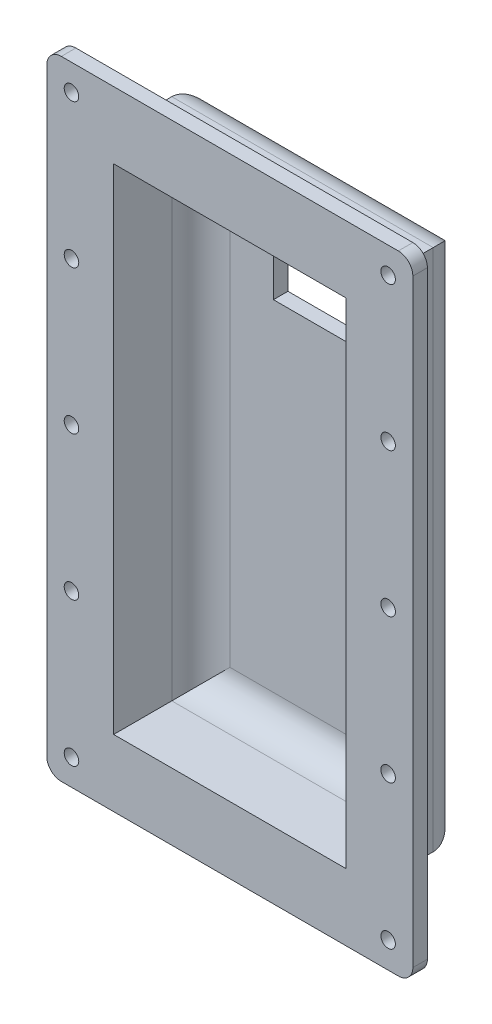
SolidWorks part; units mm, degrees
ref_plane "Front Plane" through (0, 0, 0) normal (0, 0, 1) x (1, 0, 0)
ref_plane "Top Plane" through (0, 0, 0) normal (0, 1, 0) x (1, 0, 0)
ref_plane "Right Plane" through (0, 0, 0) normal (1, 0, 0) x (0, 0, -1)
sketch "Sketch1" plane through (0, 0, 0) normal (0, 0, 1) x (1, 0, 0)
  line L1 (-22.48, 45) -> (22.48, 45)
  line L2 (-22.48, 45) -> (-22.48, -45)
  line L3 (-22.48, -45) -> (22.48, -45)
  line L4 (22.48, 45) -> (22.48, -45)
  line L5 (-22.48, 45) -> (22.48, -45) construction
  line L6 (-22.48, -45) -> (22.48, 45) construction
  point P0 (0, 0)
  dimension "D1" = 44.96
  dimension "D2" = 90
extrude "Boss-Extrude1" add sketch "Sketch1" along normal blind 15
sketch "Sketch2" plane through (0, 0, 15) normal (0, 0, 1) x (1, 0, 0)
  line L0 (-22.48, 45) -> (22.48, 45) construction
  line L1 (-31.48, 54) -> (31.48, 54)
  line L2 (-31.48, 54) -> (-31.48, -54)
  line L3 (-31.48, -54) -> (31.48, -54)
  line L4 (31.48, 54) -> (31.48, -54)
  line L5 (-31.48, 54) -> (31.48, -54) construction
  line L6 (-31.48, -54) -> (31.48, 54) construction
  line L7 (-22.48, 45) -> (-22.48, -45) construction
  point P0 (0, 0)
  point P8 (0, 45)
  dimension "D1" = 9
  dimension "D2" = 9
extrude "Boss-Extrude2" add sketch "Sketch2" along normal blind 2.5
shell "Shell1" thickness 2.5 removed face at (0, 0, 17.5)
fillet "Fillet1" radius 2.5 4 edges at (-31.48, -54, 16.25) (31.48, -54, 16.25) (31.48, 54, 16.25) (-31.48, 54, 16.25)
fillet "Fillet2" radius 5 8 edges at (0, -42.5, 2.5) (19.98, 0, 2.5) (-19.98, 0, 2.5) (0, 42.5, 2.5) (0, -45, 0) (22.48, 0, 0) (0, 45, 0) (-22.48, 0, 0)
sketch "Sketch3" plane through (0, 0, 2.5) normal (0, 0, 1) x (1, 0, 0)
  line L1 (-7.5, 29) -> (7.5, 29)
  line L2 (-7.5, 29) -> (-7.5, 21)
  line L3 (-7.5, 21) -> (7.5, 21)
  line L4 (7.5, 29) -> (7.5, 21)
  line L5 (-7.5, 29) -> (7.5, 21) construction
  line L6 (-7.5, 21) -> (7.5, 29) construction
  point P0 (0, 25)
  dimension "D1" = 8
  dimension "D2" = 15
  dimension "D3" = 25
extrude "Cut-Extrude1" cut sketch "Sketch3" against normal through all
sketch "Sketch4" plane through (0, 0, 17.5) normal (0, 0, 1) x (1, 0, 0)
  line L0 (22.48, 45) -> (22.48, -45) construction
  line L3 (-27.23, -49.5) -> (27.23, -49.5) construction
  line L10 (-27.23, -49.5) -> (-27.23, 49.5) construction
  line L11 (-27.23, 49.5) -> (27.23, 49.5) construction
  line L12 (27.23, -49.5) -> (27.23, 49.5) construction
  line L13 (-27.23, -49.5) -> (27.23, 49.5) construction
  line L14 (-27.23, 49.5) -> (27.23, -49.5) construction
  circle A16 centre (-27.23, 49.5) radius 1.25
  circle A17 centre (27.23, 49.5) radius 1.25
  circle A18 centre (27.23, 24.75) radius 1.25
  circle A19 centre (27.23, 0) radius 1.25
  circle A20 centre (27.23, -24.75) radius 1.25
  circle A21 centre (27.23, -49.5) radius 1.25
  circle A22 centre (-27.23, 24.75) radius 1.25
  circle A23 centre (-27.23, 0) radius 1.25
  circle A24 centre (-27.23, -24.75) radius 1.25
  circle A25 centre (-27.23, -49.5) radius 1.25
  point P0 (0, 0)
  dimension "D1" = 99
  dimension "D3" = 2.5
  dimension "D2" = 4.75
  dimension "D4" = 5
extrude "Cut-Extrude2" cut sketch "Sketch4" against normal up to surface (2.5 mm away) up to face at (0, 0, 15)
equation "\"case_width\"=44.96"
equation "\"D1@Sketch1\"=\"case_width\""
